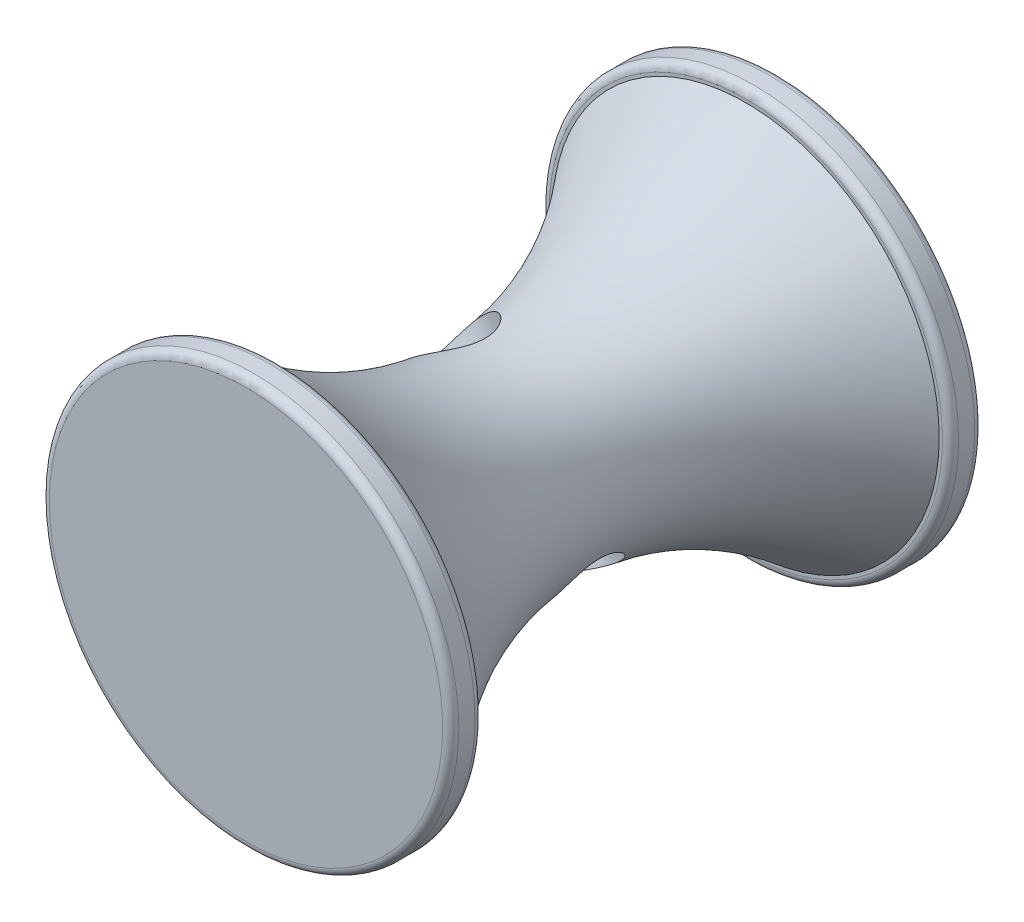
SolidWorks part; units mm, degrees
ref_plane "Front Plane" through (0, 0, 0) normal (0, 0, 1) x (1, 0, 0)
ref_plane "Top Plane" through (0, 0, 0) normal (0, 1, 0) x (1, 0, 0)
ref_plane "Right Plane" through (0, 0, 0) normal (1, 0, 0) x (0, 0, -1)
sketch "Sketch1" plane through (0, 0, 0) normal (0, 0, 1) x (1, 0, 0)
  circle A0 centre (0, 0) radius 2
  dimension "D1" = 4
sketch "Sketch10" plane through (0, 0, 0) normal (0, 1, 0) x (1, 0, 0)
  line L0 (0, 50) -> (0, -50) construction
  point P4 (0, 0)
  dimension "D1" = 100
ref_plane "Plane1" through (0, 0, 0) normal (-0.6516, 0.7586, 0) x (0, 0, 1)
sketch "Sketch3" plane through (0, 0, 0) normal (-0.6516, 0.7586, 0) x (0, 0, 1)
  line L0 (0, 0) -> (29, 0)
  line L1 (29, 0) -> (29, 12)
  line L2 (0, 0) -> (0, 12)
  line L3 (14.5, 0) -> (14.5, 6) construction
  line L5 (0, 0) -> (-2, 0)
  line L6 (0, 0) -> (0, 12.7)
  line L7 (0, 12.7) -> (-2, 12.7)
  line L8 (-2, 0) -> (-2, 12.7)
  line L9 (29, 0) -> (31, 0)
  line L10 (29, 0) -> (29, 12.7)
  line L11 (29, 12.7) -> (31, 12.7)
  line L12 (31, 0) -> (31, 12.7)
  spline S0 degree 2 poles (0, 12) (14.5, 0) (29, 12) knots 0 0 0 1 1 1
  dimension "D1" = 12
  dimension "D2" = 29
  dimension "D3" = 6
  dimension "D4" = 12.7
  dimension "D5" = 2
revolve "Revolve1" add sketch "Sketch3" angle 360 about L0 region at (3.1861, 2.7366, 6.3438) region at (4.817, 4.1375, -1) region at (3.1861, 2.7366, 22.6562) region at (4.817, 4.1375, 30)
extrude "Cut-Extrude2" cut sketch "Sketch1" against normal blind 14 and the other way blind 2 contours A0 region at (0, 0, 0)
fillet "Fillet1" radius 0.5 4 edges at (-12.7, 0, 29) (-12.7, 0, 0) (-12.7, 0, 31) (-12.7, 0, -2)
sketch "Sketch5" plane through (0, 0, 0) normal (-0.6516, 0.7586, 0) x (0, 0, 1)
  line L0 (-2, -12.7) -> (31, -12.7) construction
  line L1 (-2, 12.2) -> (-2, -12.2) construction
  line L2 (31, -12.2) -> (31, 12.2) construction
  line L3 (14.5, -12.7) -> (14.5, 12.7) construction
  line L4 (29.5, -12.7) -> (30.5, -12.7) construction
  line L5 (-2, 12.7) -> (31, 12.7) construction
  line L6 (-0.5, 12.7) -> (-1.5, 12.7) construction
  circle A0 centre (14.5, 0) radius 2.5
  point P19 (14.5, 0)
  dimension "D1" = 5
extrude "Cut-Extrude4" cut sketch "Sketch5" against normal up to surface and the other way up to surface up to face at (-12, 0, 29) other way up to face at (-12, 0, 29)
sketch "Sketch6" plane through (0, 0, -2) normal (0, 0, -1) x (-1, 0, 0)
  circle A0 centre (0, 0) radius 5
  circle A2 centre (0, 0) radius 2 construction
  dimension "D1" = 3
extrude "Boss-Extrude1" add sketch "Sketch6" along normal blind 5
sketch "Sketch8" plane through (0, 0, -7) normal (0, 0, -1) x (-1, 0, 0)
  circle A0 centre (0, 0) radius 2
  dimension "D1" = 4
extrude "Cut-Extrude5" cut sketch "Sketch8" against normal up to surface (5 mm away) up to face at (-5, 0, -2)
fillet "Fillet2" radius 0.5 3 edges at (-2, 0, -7) (-5, 0, -7) (-5, 0, -2)
sketch "Sketch9" plane through (0, 0, 0) normal (-0.6516, 0.7586, 0) x (0, 0, 1)
  line L0 (-7, 0) -> (-2, 0) construction
  line L1 (-7, 2.5) -> (-7, -2.5) construction
  line L2 (-2, 5.5) -> (-2, -5.5) construction
  circle A0 centre (-4.5, 0) radius 1.25
  dimension "D1" = 2.5
extrude "Cut-Extrude6" cut sketch "Sketch9" along normal up to next
ref_plane "Plane2" through (-3.2578, 3.7929, 0) normal (-0.6516, 0.7586, 0) x (0.7586, 0.6516, 0)
sketch "Sketch11" plane through (-3.2578, 3.7929, 0) normal (-0.6516, 0.7586, 0) x (0.7586, 0.6516, 0)
  line L0 (1.25, 4.5) -> (-1.25, 4.5) construction
  line L1 (0, 5.75) -> (0, 3.25) construction
  circle A0 centre (0, 3.25) radius 0.4
  circle A1 centre (0, 4.5) radius 1.25 construction
  circle A2 centre (0, 4.5) radius 1.25 construction
  circle A3 centre (-1.0825, 5.125) radius 0.4
  circle A4 centre (1.0825, 5.125) radius 0.4
  point P8 (-0.9982, 7.134)
  point P12 (0, 4.5)
  point P13 (1.7328, 3.7159)
  point P14 (0, 0)
  point P15 (0, 0)
  point P20 (0, 4.5)
  point P21 (0, 0)
  point P22 (0, 0)
  point P23 (0.7551, 3.5039)
  point P24 (0, 0)
  dimension "D1" = 0.8
  dimension "D2" = 3
extrude "Boss-Extrude3" add sketch "Sketch11" against normal up to surface (2.8104 mm away) from offset 0.23 contours A0 | A3 | A4 region at (-3.2578, 3.7929, -3.25) region at (-4.079, 3.0876, -5.125) region at (-2.4366, 4.4983, -5.125) up to face at (2, 0, 2) offset against normal yes
fillet "Fillet3" radius 0.25 2 edges at (-1.1402, 3.2069, -4.7511) (-2.9981, 1.6112, -4.7511)
ref_plane "Plane3" through (0, 0, 0) normal (-0.7586, -0.6516, 0) x (0, 0, 1)
sketch "Sketch12" plane through (0, 0, 0) normal (-0.7586, -0.6516, 0) x (0, 0, 1)
  line L0 (-5.75, 5) -> (-4.5, 5)
  line L1 (2.2, 5) -> (-2.2, 5) construction
  line L2 (-4.5, 5) -> (-4.5, 3.75)
  line L3 (-4.5, 3.75) -> (-5.75, 5)
  spline S0 degree 2 poles (-3.25, 5) (-4.5, 4.6875) (-5.75, 5) knots 0 0 0 1 1 1 weights 0.00375 0.005 0.00625 construction
  point P4 (0, 0)
  point P11 (0, 0)
revolve "Cut-Revolve1" cut sketch "Sketch12" angle 360 about L2
